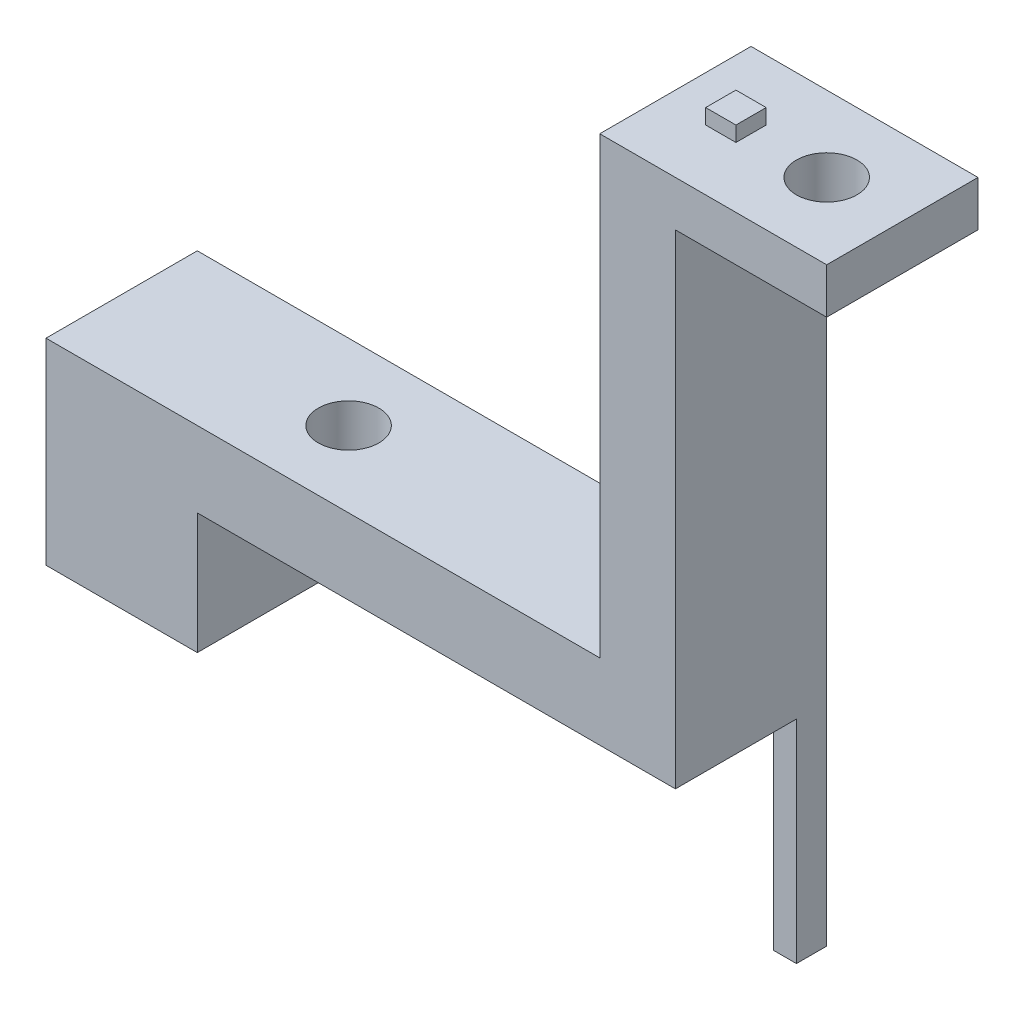
SolidWorks part; units mm, degrees
ref_plane "Front Plane" through (0, 0, 0) normal (0, 0, 1) x (1, 0, 0)
ref_plane "Top Plane" through (0, 0, 0) normal (0, 1, 0) x (1, 0, 0)
ref_plane "Right Plane" through (0, 0, 0) normal (1, 0, 0) x (0, 0, -1)
sketch "Sketch1" plane through (0, 0, 0) normal (0, 0, 1) x (1, 0, 0)
  line L0 (0, 8.6428) -> (0, -8.815) construction
  line L1 (-7.8399, 0) -> (7.1786, 0) construction
  line L2 (36.6, -2.7124) -> (36.6, 24.7717) construction
  line L3 (-5.2779, 43) -> (40.9314, 43) construction
  line L4 (10, 13) -> (36.6, 13)
  line L5 (0, 13) -> (10, 13)
  line L6 (0, 13) -> (0, 0)
  line L7 (0, 0) -> (10, 0)
  line L8 (10, 8) -> (10, 0)
  line L9 (36.6, 13) -> (36.6, 43)
  line L11 (41.6, 40) -> (41.6, 8)
  line L12 (41.6, 8) -> (10, 8)
  line L13 (41.6, 40) -> (51.6, 40)
  line L14 (51.6, 40) -> (51.6, 43)
  line L16 (36.6, 43) -> (51.6, 43)
  dimension "D4" = 30
  dimension "D1" = 36.6
  dimension "D2" = 10
  dimension "D3" = 13
  dimension "D5" = 15
  dimension "D6" = 5
  dimension "D7" = 5
  dimension "D8" = 3
  dimension "D9" = 8
  dimension "D10" = 31.6
extrude "Boss-Extrude1" add sketch "Sketch1" along normal blind 10
sketch "Sketch2" plane through (0, 0, 0) normal (0, -1, 0) x (1, 0, 0)
  line L0 (5, 15.6268) -> (5, -4.9051) construction
  line L1 (2.45, 6.55) -> (7.55, 6.55)
  line L2 (2.45, 6.55) -> (2.45, 3.45)
  line L3 (2.45, 3.45) -> (7.55, 3.45)
  line L4 (7.55, 6.55) -> (7.55, 3.45)
  line L5 (-4.1598, 5) -> (14.1324, 5) construction
  line L11 (0, 0) -> (10, 0) construction
  line L12 (0, 10) -> (0, 0) construction
  dimension "D1" = 5
  dimension "D2" = 5
  dimension "D3" = 5.1
  dimension "D4" = 3.1
extrude "Cut-Extrude1" cut sketch "Sketch2" against normal blind 10 contours L2 L1 L4 L3
sketch "Sketch3" plane through (0, 43, 0) normal (0, 1, 0) x (1, 0, 0)
  line L0 (29.4648, -5) -> (60.8247, -5) construction
  line L3 (51.6, 0) -> (36.6, 0) construction
  line L4 (51.6, -10) -> (51.6, 0) construction
  line L6 (39.6, -6) -> (41.6, -6)
  line L7 (39.6, -6) -> (39.6, -4)
  line L8 (39.6, -4) -> (41.6, -4)
  line L9 (41.6, -6) -> (41.6, -4)
  circle A0 centre (46.6, -5) radius 2
  dimension "D2" = 4
  dimension "D3" = 3
  dimension "D1" = 5
  dimension "D4" = 2
  dimension "D5" = 2
  dimension "D6" = 3
extrude "Boss-Extrude2" add sketch "Sketch3" along normal blind 1 contours L7 L6 L9 L8
sketch "Sketch11" plane through (0, 43, 0) normal (0, 1, 0) x (1, 0, 0)
  line L0 (29.4648, -5) -> (60.8247, -5) construction
  line L2 (51.6, -10) -> (51.6, 0) construction
  line L5 (39.6, -6) -> (41.6, -6) construction
  line L6 (39.6, -6) -> (41.6, -6)
  line L7 (39.6, -6) -> (39.6, -4)
  line L8 (39.6, -4) -> (41.6, -4)
  line L9 (41.6, -6) -> (41.6, -4)
  circle A0 centre (46.6, -5) radius 2
  dimension "D2" = 4
  dimension "D3" = 0
  dimension "D1" = 3
  dimension "D4" = 2
  dimension "D5" = 2
  dimension "D6" = 3
extrude "Cut-Extrude4" cut sketch "Sketch11" against normal up to next contours A0
sketch "Sketch12" plane through (0, 8, 0) normal (0, -1, 0) x (1, 0, 0)
  line L0 (10, 0) -> (41.6, 0) construction
  line L1 (41.6, 2) -> (40.1, 2)
  line L2 (41.6, 2) -> (41.6, 0)
  line L3 (41.6, 0) -> (40.1, 0)
  line L4 (40.1, 2) -> (40.1, 0)
  line L5 (41.6, 10) -> (41.6, 0) construction
  line L6 (60.8694, 4.3561) -> (126.3325, 4.3561)
  dimension "D1" = 1.5
  dimension "D2" = 2
extrude "Boss-Extrude4" add sketch "Sketch12" along normal blind 14 contours L1 L4 L0 L5 region at (40.85, 8, 1)
sketch "Sketch13" plane through (0, 13, 0) normal (0, 1, 0) x (1, 0, 0)
  line L6 (36.6, 0) -> (0, 0) construction
  line L7 (0, -10) -> (0, 0) construction
  circle A0 centre (15, -5) radius 2
  dimension "D1" = 4
  dimension "D2" = 5
  dimension "D3" = 15
extrude "Cut-Extrude6" cut sketch "Sketch13" against normal blind 3
